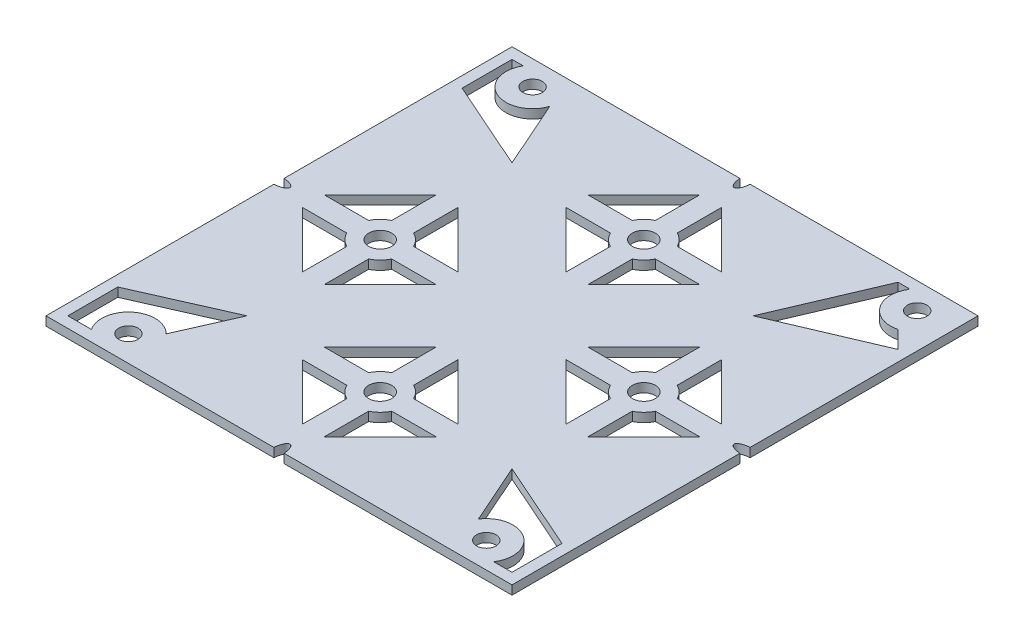
SolidWorks part; units mm, degrees
material "ABS"
ref_plane "Front Plane" through (0, 0, 0) normal (0, 0, 1) x (1, 0, 0)
ref_plane "Top Plane" through (0, 0, 0) normal (0, 1, 0) x (1, 0, 0)
ref_plane "Right Plane" through (0, 0, 0) normal (1, 0, 0) x (0, 0, -1)
sketch "Sketch1" plane through (0, 0, 0) normal (0, 1, 0) x (1, 0, 0)
  line L1 (0, 0) -> (97.6, 0)
  line L2 (0, 0) -> (0, 97.6)
  line L3 (0, 97.6) -> (97.6, 97.6)
  line L4 (97.6, 0) -> (97.6, 97.6)
  dimension "D1" = 97.6
  dimension "D2" = 97.6
extrude "Boss-Extrude1" add sketch "Sketch1" along normal blind 1.85
sketch "Sketch2" plane through (0, 0, 0) normal (0, -1, 0) x (-1, 0, 0)
  line L0 (-97.6, 97.6) -> (0, 0) construction
  line L1 (-97.6, 0) -> (0, 97.6) construction
  line L2 (-48.8, 97.6) -> (-48.8, 0) construction
  line L3 (-97.6, 97.6) -> (0, 97.6) construction
  line L4 (0, 0) -> (-97.6, 0) construction
  line L5 (-97.6, 48.8) -> (0, 48.8) construction
  line L6 (-97.6, 0) -> (-97.6, 97.6) construction
  line L7 (0, 97.6) -> (0, 0) construction
sketch "Sketch3" plane through (0, 0, 0) normal (0, -1, 0) x (1, 0, 0)
  line L0 (97.6, -97.6) -> (0, -97.6) construction
  line L1 (97.6, 0) -> (97.6, -97.6) construction
  line L2 (0, -97.6) -> (0, 0) construction
  line L3 (0, 0) -> (97.6, 0) construction
  line L4 (97.6, -94.6) -> (0, -94.6) construction
  line L5 (3, -97.6) -> (3, 0) construction
  line L6 (3, -94.6) -> (5.3161, -94.6)
  line L7 (3, -94.6) -> (3, -84.3)
  line L8 (3, -84.3) -> (21.4728, -76.1272)
  line L9 (97.6, 0) -> (0, -97.6) construction
  line L10 (21.4728, -76.1272) -> (13.3, -94.6)
  line L11 (21.4728, -21.4728) -> (13.3, -3)
  line L12 (3, -3) -> (13.3, -3)
  line L13 (0, -3) -> (97.6, -3) construction
  line L14 (3, -13.3) -> (3, -3)
  line L15 (3, -3) -> (7.8732, -3)
  line L16 (3, -13.3) -> (21.4728, -21.4728)
  line L17 (97.6, -97.6) -> (0, 0) construction
  line L18 (0, -97.6) -> (0, 0) construction
  line L19 (16.1614, -10.109) -> (21.4728, -21.4728) construction
  line L20 (94.6, -97.6) -> (94.6, 0) construction
  line L21 (94.6, -3) -> (94.6, -13.3)
  line L22 (94.6, -3) -> (84.3, -3)
  line L23 (94.6, -13.3) -> (76.1272, -21.4728)
  line L24 (76.1272, -21.4728) -> (84.3, -3)
  line L25 (94.6, -82.6) -> (73.6741, -73.6741)
  line L26 (73.6741, -73.6741) -> (82.6, -94.6)
  line L27 (94.6, -82.6) -> (82.6, -94.6) construction
  line L28 (94.6, -82.6) -> (91.0273, -86.1727)
  line L29 (82.6, -94.6) -> (85.1169, -94.6)
  line L30 (3, -94.6) -> (13.3, -94.6) construction
  circle A0 centre (89.66, -91.5) radius 1.25
  circle A1 centre (10.05, -91.8) radius 1.25
  circle A2 centre (12.45, -6.05) radius 1.25
  circle A3 centre (86.25, -6.05) radius 1.25
  circle A4 centre (89.66, -91.5) radius 5.5
  circle A5 centre (10.05, -91.8) radius 5.5
  circle A6 centre (12.45, -6.05) radius 5.5
  circle A7 centre (86.25, -6.05) radius 5.5
  dimension "D1" = 6.1
  dimension "D9" = 3
  dimension "D16" = 3
  dimension "D20" = 2.5
  dimension "D21" = 11
  dimension "D23" = 11
  dimension "D24" = 2.5
  dimension "D26" = 11
  dimension "D27" = 11
  dimension "D2" = 7.94
  dimension "D3" = 5.8
  dimension "D4" = 10.05
  dimension "D5" = 6.05
  dimension "D6" = 12.45
  dimension "D7" = 6.05
  dimension "D8" = 11.35
  dimension "D10" = 3
  dimension "D11" = 10.3
  dimension "D12" = 20.2
  dimension "D13" = 3
  dimension "D14" = 10.3
  dimension "D15" = 20.2
  dimension "D17" = 10.3
  dimension "D18" = 22.75
  dimension "D19" = 15
  dimension "D22" = 10.3
  dimension "D25" = 20.2
extrude "Cut-Extrude1" cut sketch "Sketch3" against normal blind 10 contours A2 | A1 | A1 | A5 L8 L7 L6 | A4 L28 L25 L26 L29 | A3 | A7 L24 L23 L21 L22 | A6 L15 L14 L16 | A0 region at (11.5662, 0, -84.2704) region at (10.6634, 0, -12.5774) region at (86.5986, 0, -12.9459) region at (83.266, 0, -83.1897) region at (10.05, 0, -91.8) region at (12.45, 0, -6.05) region at (86.25, 0, -6.05)
fillet "Fillet1" radius 0.2 1 edges at (85.1169, 0.925, -94.6)
sketch "Sketch5" plane through (0, 0, 0) normal (0, -1, 0) x (1, 0, 0)
  line L0 (78.0601, -69.3344) -> (24.4532, -15.7275) construction
  line L1 (15.9101, -24.6358) -> (67.2589, -75.9846) construction
  line L2 (97.6, -97.6) -> (0, 0) construction
  line L3 (25.594, -80.7317) -> (80.9701, -25.3556) construction
  line L4 (71.5743, -17.3) -> (16.8047, -72.0696) construction
  line L5 (97.6, 0) -> (0, -97.6) construction
  line L6 (51.05, -89.7671) -> (51.05, -80.6171)
  line L7 (46.55, -89.7671) -> (46.55, -80.6171)
  line L8 (48.8, -97.6) -> (48.8, 0) construction
  line L9 (51.05, -89.7671) -> (62.5825, -78.2346)
  line L10 (62.5825, -78.2346) -> (53.4325, -78.2346)
  line L11 (44.1675, -78.2346) -> (35.0175, -78.2346)
  line L12 (35.0175, -78.2346) -> (46.55, -89.7671)
  line L13 (48.8, -78.2346) -> (36.0473, -78.2346) construction
  line L14 (48.8, -73.7346) -> (36.0473, -73.7346) construction
  line L15 (44.1675, -73.7346) -> (35.0175, -73.7346)
  line L16 (46.55, -71.3521) -> (46.55, -62.2021)
  line L17 (53.4325, -73.7346) -> (62.5825, -73.7346)
  line L18 (51.05, -71.3521) -> (51.05, -62.2021)
  line L19 (62.5825, -73.7346) -> (51.05, -62.2021)
  line L20 (46.55, -62.2021) -> (35.0175, -73.7346)
  line L21 (48.8, -48.8) -> (-2.5605, -100.1605) construction
  line L22 (48.8, -48.8) -> (97.6, 0) construction
  line L23 (97.6, -97.6) -> (0, 0) construction
  line L24 (73.7346, -48.8) -> (73.7346, -36.0473) construction
  line L25 (78.2346, -48.8) -> (78.2346, -36.0473) construction
  line L26 (62.2021, -46.55) -> (73.7346, -35.0175)
  line L27 (73.7346, -62.5825) -> (62.2021, -51.05)
  line L28 (71.3521, -51.05) -> (62.2021, -51.05)
  line L29 (73.7346, -53.4325) -> (73.7346, -62.5825)
  line L30 (71.3521, -46.55) -> (62.2021, -46.55)
  line L31 (73.7346, -44.1675) -> (73.7346, -35.0175)
  line L32 (78.2346, -35.0175) -> (89.7671, -46.55)
  line L33 (78.2346, -44.1675) -> (78.2346, -35.0175)
  line L34 (78.2346, -62.5825) -> (78.2346, -53.4325)
  line L35 (89.7671, -51.05) -> (78.2346, -62.5825)
  line L36 (89.7671, -46.55) -> (80.6171, -46.55)
  line L37 (89.7671, -51.05) -> (80.6171, -51.05)
  line L38 (48.8, -19.3654) -> (61.5527, -19.3654) construction
  line L39 (48.8, -23.8654) -> (61.5527, -23.8654) construction
  line L40 (23.8654, -48.8) -> (23.8654, -61.5527) construction
  line L41 (19.3654, -48.8) -> (19.3654, -61.5527) construction
  line L42 (46.55, -7.8329) -> (46.55, -16.9829)
  line L43 (51.05, -7.8329) -> (51.05, -16.9829)
  line L44 (46.55, -7.8329) -> (35.0175, -19.3654)
  line L45 (35.0175, -19.3654) -> (44.1675, -19.3654)
  line L46 (53.4325, -19.3654) -> (62.5825, -19.3654)
  line L47 (62.5825, -19.3654) -> (51.05, -7.8329)
  line L48 (53.4325, -23.8654) -> (62.5825, -23.8654)
  line L49 (51.05, -26.2479) -> (51.05, -35.3979)
  line L50 (44.1675, -23.8654) -> (35.0175, -23.8654)
  line L51 (46.55, -26.2479) -> (46.55, -35.3979)
  line L52 (35.0175, -23.8654) -> (46.55, -35.3979)
  line L53 (51.05, -35.3979) -> (62.5825, -23.8654)
  line L54 (35.3979, -51.05) -> (23.8654, -62.5825)
  line L55 (23.8654, -35.0175) -> (35.3979, -46.55)
  line L56 (26.2479, -46.55) -> (35.3979, -46.55)
  line L57 (23.8654, -44.1675) -> (23.8654, -35.0175)
  line L58 (26.2479, -51.05) -> (35.3979, -51.05)
  line L59 (23.8654, -53.4325) -> (23.8654, -62.5825)
  line L60 (19.3654, -62.5825) -> (7.8329, -51.05)
  line L61 (19.3654, -53.4325) -> (19.3654, -62.5825)
  line L62 (19.3654, -35.0175) -> (19.3654, -44.1675)
  line L63 (7.8329, -46.55) -> (19.3654, -35.0175)
  line L64 (7.8329, -51.05) -> (16.9829, -51.05)
  line L65 (7.8329, -46.55) -> (16.9829, -46.55)
  line L66 (49.9, -97.6) -> (47.7, -97.6)
  line L67 (97.6, -97.6) -> (0, -97.6) construction
  line L68 (97.6, -48.8) -> (97.6, -49.9)
  line L69 (97.6, 0) -> (97.6, -97.6) construction
  line L70 (97.6, -48.8) -> (97.6, -47.7)
  line L71 (0, -49.9) -> (0, -48.8)
  line L72 (0, -97.6) -> (0, 0) construction
  line L73 (0, -48.8) -> (0, -47.7)
  line L74 (48.8, 0) -> (49.9, 0)
  line L75 (0, 0) -> (97.6, 0) construction
  line L76 (48.8, 0) -> (47.7, 0)
  circle A0 centre (48.8, -75.9846) radius 2.375
  circle A1 centre (48.8, -75.9846) radius 5.15
  circle A2 centre (75.9846, -48.8) radius 5.15
  circle A3 centre (75.9846, -48.8) radius 2.375
  circle A4 centre (48.8, -21.6154) radius 2.375
  circle A5 centre (48.8, -21.6154) radius 5.15
  circle A6 centre (21.6154, -48.8) radius 5.15
  circle A7 centre (21.6154, -48.8) radius 2.375
  ellipse E0 centre (48.8, -97.6) end of major axis (48.8, -94.6046) minor radius 1.1
  ellipse E1 centre (97.6, -48.8) end of major axis (94.5962, -48.8) minor radius 1.1
  ellipse E2 centre (0, -48.8) end of major axis (3, -48.8) minor radius 1.1
  ellipse E3 centre (48.8, 0) end of major axis (48.8, -3) minor radius 1.1
  line M15 (0, 0) -> (0, -97.6)
  line M16 (0, -97.6) -> (97.6, -97.6)
  line M17 (97.6, -97.6) -> (97.6, 0)
  line M18 (97.6, 0) -> (0, 0)
  dimension "D5" = 9.15
  dimension "D7" = 4.75
  dimension "D8" = 10.3
  dimension "D1" = 6.17
  dimension "D2" = 6.17
  dimension "D3" = 6.17
  dimension "D4" = 6.17
  dimension "D6" = 2.25
  dimension "D9" = 2.25
  dimension "D10" = 1.1
  dimension "D11" = 1.1
  dimension "D12" = 1.1
  dimension "D13" = 3
  dimension "D14" = 2.25
  dimension "D15" = 2.25
  dimension "D16" = 3
extrude "Cut-Extrude2" cut sketch "Sketch5" against normal blind 10 contours A1 L6 L9 L10 | A1 L11 L12 L7 | A0 | A1 L17 L19 L18 | A1 L16 L20 L15 | L61 A6 L64 L60 | L58 A6 L59 L54 | L57 A6 L56 L55 | L65 A6 L62 L63 | A7 | A3 | L37 A2 L34 L35 | L29 A2 L28 L27 | L30 A2 L31 L26 | L33 A2 L36 L32 | A5 L42 L44 L45 | A5 L46 L47 L43 | A5 L49 L53 L48 | A5 L50 L52 L51 | E0 M16 | E3 M18 | E1 M17 | E2 M15 | A4 region at (55.0576, 0, -82.2422) region at (42.5424, 0, -82.2422) region at (42.5424, 0, -69.7269) region at (55.0576, 0, -69.7269) region at (69.7269, 0, -42.5424) region at (69.7269, 0, -55.0576) region at (82.2422, 0, -42.5424) region at (82.2422, 0, -55.0576) region at (42.5424, 0, -15.3578) region at (55.0576, 0, -15.3578) region at (42.5424, 0, -27.8731) region at (55.0576, 0, -27.8731) region at (27.8731, 0, -55.0576) region at (15.3578, 0, -55.0576) region at (27.8731, 0, -42.5424) region at (15.3578, 0, -42.5424) region at (48.8, 0, -96.3287) region at (96.3251, 0, -48.8) region at (1.2732, 0, -48.8) region at (48.8, 0, -1.2732) region at (48.8, 0, -75.9846) region at (75.9846, 0, -48.8) region at (21.6154, 0, -48.8)
sketch "Sketch6" plane through (0, 0, 0) normal (0, -1, 0) x (1, 0, 0)
  circle A0 centre (12.45, -6.05) radius 2
  circle A1 centre (86.25, -6.05) radius 2
  circle A2 centre (10.05, -91.8) radius 2
  circle A3 centre (89.66, -91.5) radius 2
  dimension "D1" = 4
  dimension "D2" = 4
  dimension "D3" = 4
  dimension "D4" = 4
extrude "Cut-Extrude3" cut sketch "Sketch6" against normal through all
sketch "Sketch7" plane through (0, 0, -97.6) normal (0, 0, -1) x (-1, 0, 0)
  line L1 (0, 0) -> (-97.6, 0)
  line L2 (0, 0) -> (0, 1.85)
  line L3 (0, 1.85) -> (-97.6, 1.85)
  line L4 (-97.6, 0) -> (-97.6, 1.85)
extrude "Cut-Extrude4" cut sketch "Sketch7" against normal blind 0.75
sketch "Sketch8" plane through (97.6, 0, 0) normal (1, 0, 0) x (0, 0, -1)
  line L1 (96.85, 0) -> (0, 0)
  line L2 (96.85, 0) -> (96.85, 1.85)
  line L3 (96.85, 1.85) -> (0, 1.85)
  line L4 (0, 0) -> (0, 1.85)
extrude "Cut-Extrude5" cut sketch "Sketch8" against normal blind 0.75
sketch "Sketch9" plane through (0, 0, 0) normal (0, 0, 1) x (1, 0, 0)
  line L1 (0, 0) -> (96.85, 0)
  line L2 (0, 0) -> (0, 1.85)
  line L3 (0, 1.85) -> (96.85, 1.85)
  line L4 (96.85, 0) -> (96.85, 1.85)
extrude "Cut-Extrude6" cut sketch "Sketch9" against normal blind 0.75
sketch "Sketch12" plane through (0, 0, 0) normal (-1, 0, 0) x (0, 0, 1)
  line L1 (-0.75, 0) -> (-96.85, 0)
  line L2 (-0.75, 0) -> (-0.75, 1.85)
  line L3 (-0.75, 1.85) -> (-96.85, 1.85)
  line L4 (-96.85, 0) -> (-96.85, 1.85)
extrude "Cut-Extrude7" cut sketch "Sketch12" against normal blind 0.75
